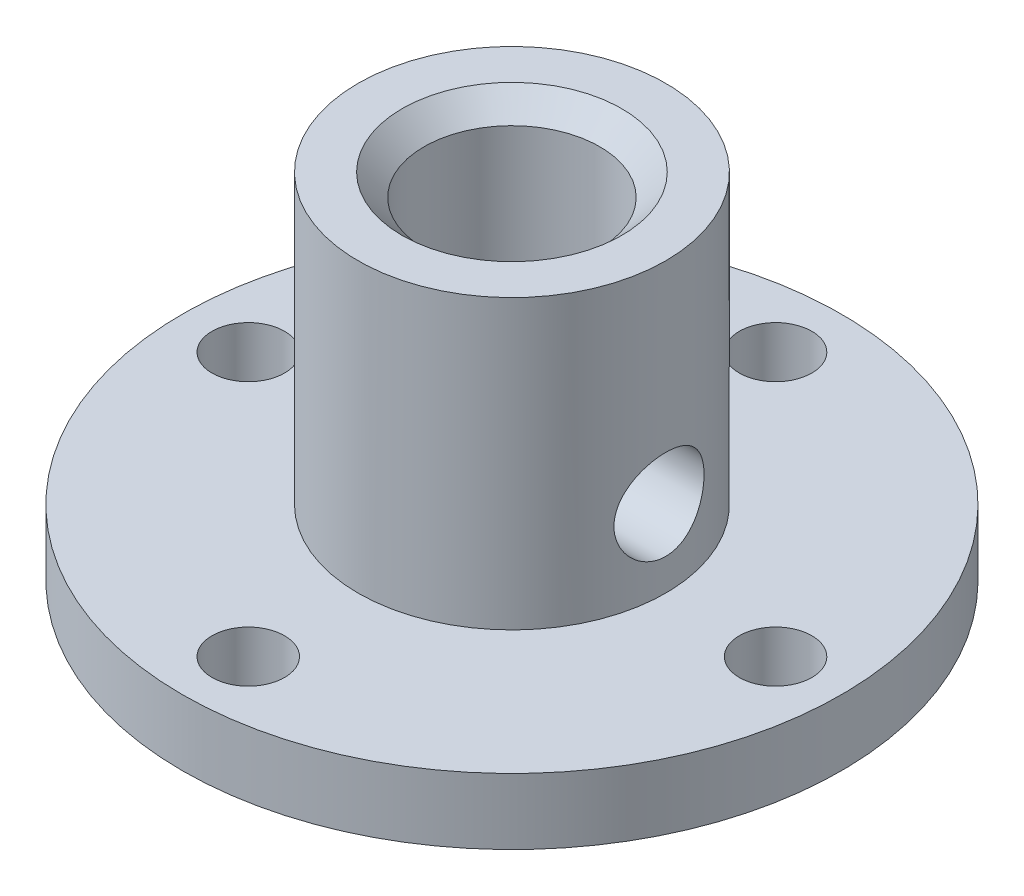
SolidWorks part; units mm, degrees
ref_plane "前视基准面" through (0, 0, 0) normal (0, 0, 1) x (1, 0, 0)
ref_plane "上视基准面" through (0, 0, 0) normal (0, 1, 0) x (1, 0, 0)
ref_plane "右视基准面" through (0, 0, 0) normal (1, 0, 0) x (0, 0, -1)
sketch "草图1" plane through (0, 0, 0) normal (0, 1, 0) x (1, 0, 0)
  circle A0 centre (0, 0) radius 15
  circle A1 centre (0, 0) radius 4
  dimension "D1" = 30
  dimension "D2" = 8
extrude "凸台-拉伸1" add sketch "草图1" along normal blind 3 contours A1 | A0 region at (0, 0, 0)
sketch "草图2" plane through (0, 3, 0) normal (0, 1, 0) x (1, 0, 0)
  circle A0 centre (0, 0) radius 4
  circle A1 centre (0, 0) radius 7
  dimension "D1" = 14
  dimension "D2" = 8
extrude "凸台-拉伸2" add sketch "草图2" along normal up to surface (13.1 mm away)
ref_axis "基准轴1" through (0, 9, 0) along (0, -1, 0)
sketch "草图4" plane through (0, 0, 0) normal (0, -1, 0) x (-1, 0, 0)
  line L0 (0, 0) -> (0, -10.4165)
ref_plane "基准面1" through (0, 0, 0) normal (-1, 0, 0) x (0, 0, 1)
sketch "草图5" plane through (0, 0, 0) normal (-1, 0, 0) x (0, 0, 1)
  line L1 (-7, 16.1) -> (-7, 3) construction
  line L2 (7, 3) -> (-7, 3) construction
  circle A0 centre (0, 6.5) radius 2.05
  dimension "D1" = 4.1
  dimension "D2" = 3.5
  dimension "D3" = 7
extrude "切除-拉伸1" cut sketch "草图5" along normal through all and the other way blind 10
sketch "草图6" plane through (0, 0, 0) normal (0, -1, 0) x (1, 0, 0)
  circle A0 centre (0, 0) radius 4
  dimension "D1" = 8
sketch "草图7" plane through (0, 3, 0) normal (0, 1, 0) x (1, 0, 0)
  circle A0 centre (0, -12) radius 1.65
  circle A1 centre (-12, 0) radius 1.65
  circle A2 centre (0, 12) radius 1.65
  circle A3 centre (12, 0) radius 1.65
  point P12 (0, 0)
  dimension "D1" = 0
  dimension "D2" = 12
  dimension "D3" = 3.3
  dimension "D4" = 4
extrude "切除-拉伸3" cut sketch "草图7" against normal blind 4 contours A3 | A0 | A1 | A2 region at (12, 3, 0)
chamfer "倒角1" distance 1 angle 45 1 edges at (-4, 16.1, 0)
